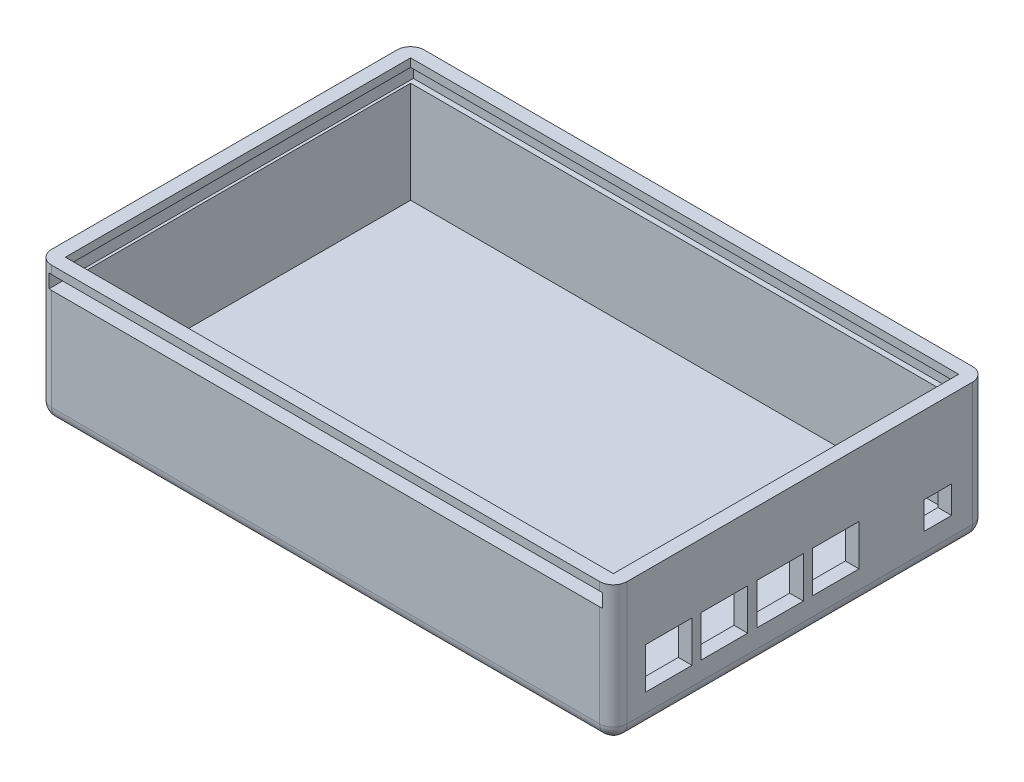
SolidWorks part; units mm, degrees
ref_plane "Front Plane" through (0, 0, 0) normal (0, 0, 1) x (1, 0, 0)
ref_plane "Top Plane" through (0, 0, 0) normal (0, 1, 0) x (1, 0, 0)
ref_plane "Right Plane" through (0, 0, 0) normal (1, 0, 0) x (0, 0, -1)
sketch "Sketch1" plane through (0, 0, 0) normal (0, 1, 0) x (1, 0, 0)
  line L1 (0, 0) -> (200, 0)
  line L2 (0, 0) -> (0, 126)
  line L3 (0, 126) -> (200, 126)
  line L4 (200, 0) -> (200, 126)
  dimension "D1" = 200
  dimension "D2" = 126
extrude "Extrude-Thin1" add sketch "Sketch1" along normal blind 50 thin thin type one direction wall 5
extrude "Boss-Extrude1" add sketch "Sketch1<2>" along normal blind 5
sketch "Sketch1<2>" plane through (0, 0, 0) normal (0, 1, 0) x (1, 0, 0) same geometry as "Sketch1"
fillet "Fillet1" radius 5 8 edges at (-5, 0, -63) (-5, 25, -131) (100, 0, -131) (205, 25, -131) (205, 0, -63) (205, 25, 5) (100, 0, 5) (-5, 25, 5)
sketch "Sketch2" plane through (0, 0, 5) normal (0, 0, 1) x (1, 0, 0)
  line L0 (0, 5) -> (200, 5) construction
  line L1 (-1, 47) -> (201, 47)
  line L2 (-1, 47) -> (-1, 42)
  line L3 (-1, 42) -> (201, 42)
  line L4 (201, 47) -> (201, 42)
  line L5 (200, 0) -> (0, 0) construction
  point P4 (100, 5)
  dimension "D1" = 202
  dimension "D2" = 101
  dimension "D3" = 5
  dimension "D4" = 42
extrude "Cut-Extrude1" cut sketch "Sketch2" against normal blind 133
sketch "Sketch3" plane through (205, 0, 0) normal (1, 0, 0) x (0, 0, -1)
  line L0 (126, 0) -> (0, 0) construction
  line L1 (6.69, 26.67) -> (23.69, 26.67)
  line L2 (6.69, 26.67) -> (6.69, 11.67)
  line L3 (6.69, 11.67) -> (23.69, 11.67)
  line L4 (23.69, 26.67) -> (23.69, 11.67)
  line L5 (-5, 5) -> (-5, 42) construction
  line L7 (27.01, 26.67) -> (44.01, 26.67)
  line L8 (27.01, 26.67) -> (27.01, 11.67)
  line L9 (27.01, 11.67) -> (44.01, 11.67)
  line L10 (44.01, 26.67) -> (44.01, 11.67)
  line L11 (47.33, 26.67) -> (64.33, 26.67)
  line L12 (47.33, 26.67) -> (47.33, 11.67)
  line L13 (47.33, 11.67) -> (64.33, 11.67)
  line L14 (64.33, 26.67) -> (64.33, 11.67)
  line L15 (67.65, 26.67) -> (84.65, 26.67)
  line L16 (67.65, 26.67) -> (67.65, 11.67)
  line L17 (67.65, 11.67) -> (84.65, 11.67)
  line L18 (84.65, 26.67) -> (84.65, 11.67)
  line L19 (108.435, 11.67) -> (118.435, 11.67)
  line L20 (108.435, 11.67) -> (108.435, 21.67)
  line L21 (108.435, 21.67) -> (118.435, 21.67)
  line L22 (118.435, 11.67) -> (118.435, 21.67)
  dimension "D1" = 17
  dimension "D2" = 15
  dimension "D3" = 11.67
  dimension "D4" = 28.69
  dimension "D5" = 17
  dimension "D6" = 17
  dimension "D7" = 17
  dimension "D8" = 3.32
  dimension "D9" = 3.32
  dimension "D10" = 15
  dimension "D11" = 10
  dimension "D12" = 10
  dimension "D13" = 11.67
  dimension "D14" = 23.785
  dimension "D15" = 3.32
  dimension "D16" = 15
  dimension "D17" = 15
  dimension "D18" = 11.67
  dimension "D19" = 11.67
extrude "Cut-Extrude2" cut sketch "Sketch3" against normal blind 10
